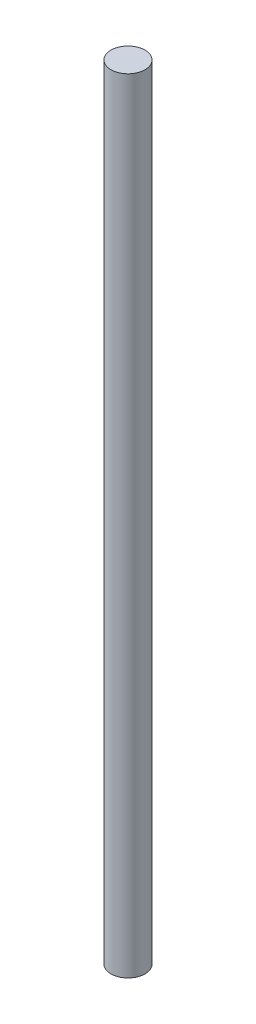
SolidWorks part; units mm, degrees
material "AISI 304"
ref_plane "Front Plane" through (0, 0, 0) normal (0, 0, 1) x (1, 0, 0)
ref_plane "Top Plane" through (0, 0, 0) normal (0, 1, 0) x (1, 0, 0)
ref_plane "Right Plane" through (0, 0, 0) normal (1, 0, 0) x (0, 0, -1)
sketch "Sketch1" plane through (0, 0, 0) normal (0, 1, 0) x (1, 0, 0)
  circle A0 centre (0, 0) radius 3
  dimension "D1" = 6
extrude "Boss-Extrude1" add sketch "Sketch1" along normal blind 138
